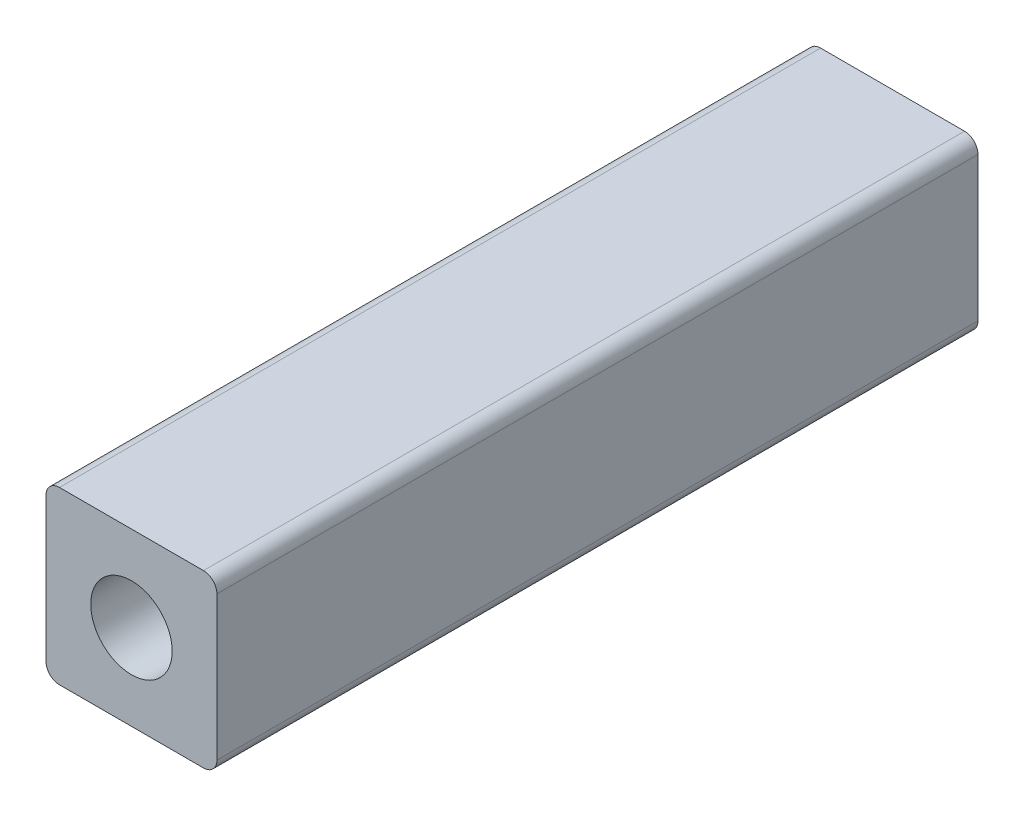
SolidWorks part; units mm, degrees
material "ABS"
ref_plane "X-Y Datum" through (0, 0, 0) normal (0, 0, 1) x (1, 0, 0)
ref_plane "X-Z Datum" through (0, 0, 0) normal (0, 1, 0) x (1, 0, 0)
ref_plane "Y-Z Datum" through (0, 0, 0) normal (1, 0, 0) x (0, 0, -1)
sketch "Sketch1" plane through (0, 0, 0) normal (0, 0, 1) x (1, 0, 0)
  line L1 (-6.35, 6.35) -> (6.35, 6.35)
  line L2 (-6.35, 6.35) -> (-6.35, -6.35)
  line L3 (-6.35, -6.35) -> (6.35, -6.35)
  line L4 (6.35, 6.35) -> (6.35, -6.35)
  line L5 (-6.35, 6.35) -> (6.35, -6.35) construction
  line L6 (-6.35, -6.35) -> (6.35, 6.35) construction
  circle A0 centre (0, 0) radius 3.025
  point P0 (0, 0)
  dimension "D1" = 6.05
  dimension "D2" = 12.7
  dimension "D3" = 12.7
extrude "Boss-Extrude1" add sketch "Sketch1" along normal mid plane 56.55
fillet "Fillet2" radius 1 4 edges at (-6.35, -6.35, 0) (-6.35, 6.35, 0) (6.35, 6.35, 0) (6.35, -6.35, 0)
